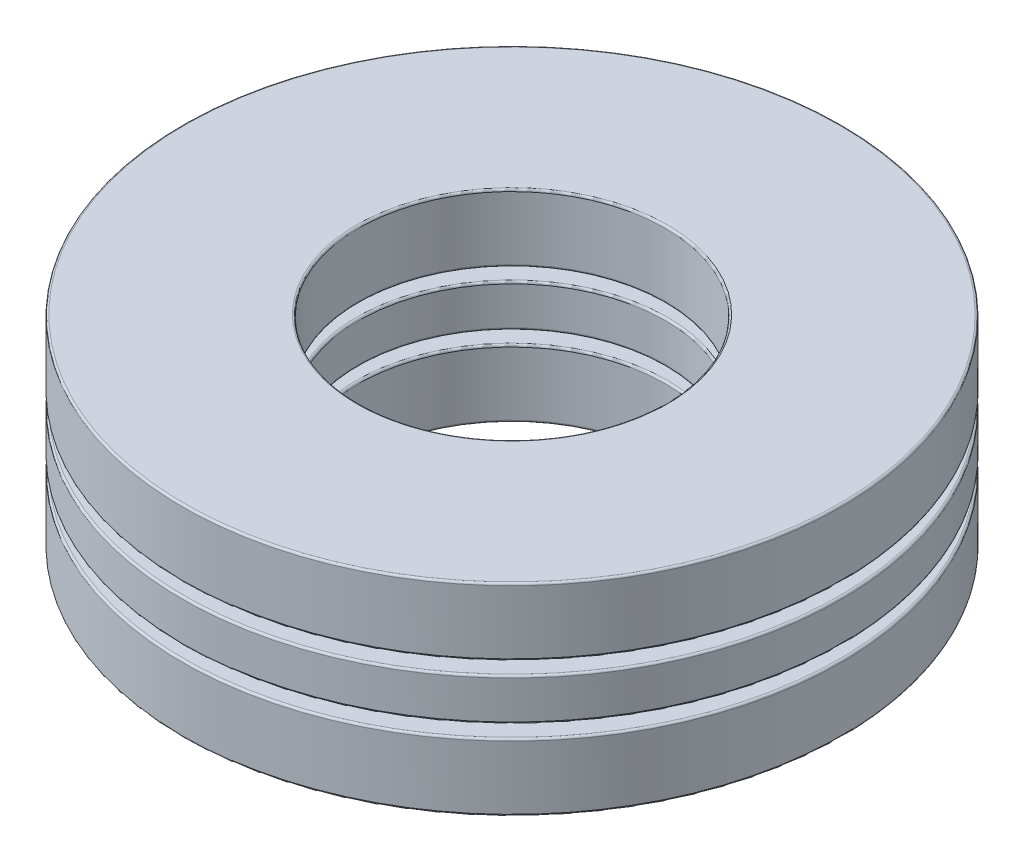
SolidWorks part; units mm, degrees
material "AISI 316 Annealed Stainless Steel Bar (SS)"
ref_plane "Front Plane" through (0, 0, 0) normal (0, 0, 1) x (1, 0, 0)
ref_plane "Top Plane" through (0, 0, 0) normal (0, 1, 0) x (1, 0, 0)
ref_plane "Right Plane" through (0, 0, 0) normal (1, 0, 0) x (0, 0, -1)
sketch "Sketch1" plane through (0, 0, 0) normal (1, 0, 0) x (0, 0, -1)
  line L0 (-10.3187, 0) -> (10.3187, 0) construction
  line L1 (0, -3.1623) -> (0, 3.1623) construction
  line L2 (-10.3187, 0.6588) -> (-4.8006, 0.6588)
  line L3 (-10.3187, 0.6588) -> (-10.3187, -0.6588)
  line L4 (-10.3187, -0.6588) -> (-4.8006, -0.6588)
  line L5 (-4.8006, 0.6588) -> (-4.8006, -0.6588)
  line L6 (-7.5597, 1.0541) -> (-7.5597, -1.0541) construction
  circle A0 centre (-7.5597, 0) radius 1.0541 construction
  point P13 (-7.5597, 0.6588)
  dimension "OD" = 20.6375
  dimension "Shaft Dia" = 9.6012
  dimension "Th" = 6.3246
  dimension "D1" = 2.1082
  dimension "D2" = 1.3176
revolve "Revolve1" add sketch "Sketch1" angle 360 about L1
sketch "Sketch3" plane through (0, 0, 0) normal (1, 0, 0) x (0, 0, -1)
  line L0 (-7.5597, 1.0541) -> (-7.5597, -1.0541)
  arc A0 (-7.5597, 1.0541) -> (-7.5597, -1.0541) centre (-7.5597, 0) ccw
  circle A1 centre (-7.5597, 0) radius 1.0541 construction
revolve "Cut-Revolve1" cut sketch "Sketch3" angle 360 about L0
sketch "Sketch2" plane through (0, 0, 0) normal (1, 0, 0) x (0, 0, -1)
  line L0 (-7.5597, 1.0541) -> (-7.5597, -1.0541)
  arc A0 (-7.5597, 1.0541) -> (-7.5597, -1.0541) centre (-7.5597, 0) ccw
  circle A2 centre (-7.5597, 0) radius 1.0541 construction
revolve "Revolve2" add sketch "Sketch2" angle 360 about L0
ref_axis "Axis1" through (0, 3.1623, 0) along (0, -1, 0)
pattern_circular "CirPattern1" count 4 every 90 about axis through (0, 3.1623, 0) along (0, -1, 0) of bodies 187
pattern_circular "CirPattern2" count 4 every 90 about axis through (0, 3.1623, 0) along (0, -1, 0) of "Cut-Revolve1"
sketch "Sketch4" plane through (0, 0, 0) normal (1, 0, 0) x (0, 0, -1)
  line L0 (-10.3187, 0.6588) -> (-10.3187, -0.6588) construction
  line L1 (-10.3187, 1.0541) -> (-4.8006, 1.0541)
  line L2 (-10.3187, 1.0541) -> (-10.3187, 3.1623)
  line L3 (-10.3187, 3.1623) -> (-4.8006, 3.1623)
  line L4 (-4.8006, 1.0541) -> (-4.8006, 3.1623)
  line L5 (-10.3187, -3.1623) -> (-4.8006, -3.1623)
  line L6 (-10.3187, -3.1623) -> (-10.3187, -1.0541)
  line L7 (-10.3187, -1.0541) -> (-4.8006, -1.0541)
  line L8 (-4.8006, -3.1623) -> (-4.8006, -1.0541)
  line L9 (-7.5597, 1.0541) -> (-7.5597, -1.0541) construction
  line L10 (-4.8006, 0.6588) -> (-4.8006, -0.6588) construction
  line L11 (0, 0) -> (-10.3187, 0) construction
  line L12 (-10.3187, 0) -> (10.3187, 0) construction
  dimension "Ht" = 6.3246
revolve "Revolve3" add sketch "Sketch4" angle 360 about L1
fillet "Fillet1" radius 0.0632 4 edges at (0, 1.0541, -4.8006) (0, 3.1623, -4.8006) (0, 1.0541, -10.3187) (0, 3.1623, -10.3187)
fillet "Fillet2" radius 0.0632 4 edges at (0, -0.6588, -4.8006) (0, 0.6588, -4.8006) (0, -0.6588, -10.3187) (0, 0.6588, -10.3187)
fillet "Fillet3" radius 0.0632 4 edges at (0, -3.1623, -4.8006) (0, -1.0541, -4.8006) (0, -3.1623, -10.3187) (0, -1.0541, -10.3187)
equation "\"D1@Sketch1\" = \"Th@Sketch1\"/3"
equation "\"D2@Sketch1\" = \"D1@Sketch1\"*.625"
equation "\"Balls@CirPattern1\" = \"OD@Sketch1\"*5"
equation "\"Angle@CirPattern1\" = 360/\"Balls@CirPattern1\""
equation "\"D1@CirPattern2\" = \"Balls@CirPattern1\""
equation "\"D2@CirPattern2\" = \"Angle@CirPattern1\""
equation "\"D1@Fillet1\" = \"Th@Sketch1\"*.01"
equation "\"D1@Fillet2\" = \"D1@Fillet1\""
equation "\"D1@Fillet3\" = \"D1@Fillet1\""
